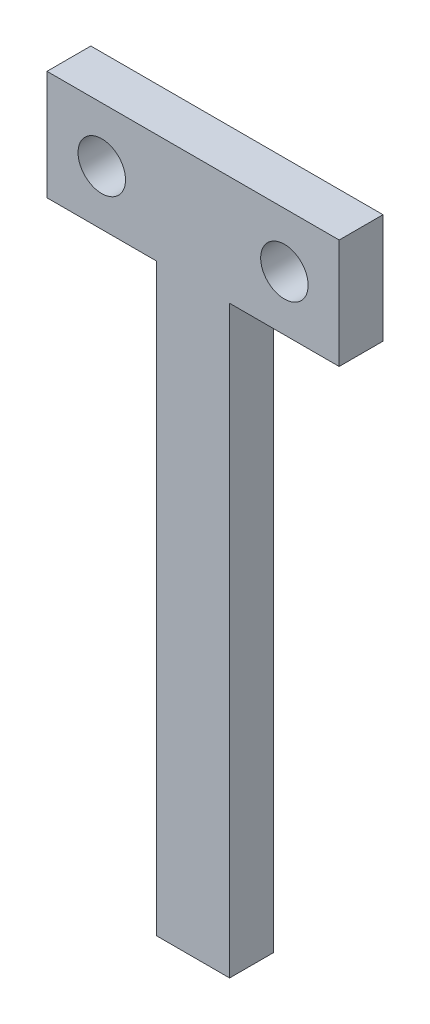
SolidWorks part; units mm, degrees
ref_plane "Front Plane" through (0, 0, 0) normal (0, 0, 1) x (1, 0, 0)
ref_plane "Top Plane" through (0, 0, 0) normal (0, 1, 0) x (1, 0, 0)
ref_plane "Right Plane" through (0, 0, 0) normal (1, 0, 0) x (0, 0, -1)
sketch "Sketch1" plane through (0, 0, 0) normal (0, 0, 1) x (1, 0, 0)
  line L0 (0, 0) -> (0, 40)
  line L1 (0, 40) -> (-7.5, 40)
  line L2 (-7.5, 40) -> (-7.5, 47.5)
  line L3 (-7.5, 47.5) -> (12.5, 47.5)
  line L4 (12.5, 47.5) -> (12.5, 40)
  line L5 (12.5, 40) -> (5, 40)
  line L6 (5, 40) -> (5, 0)
  line L7 (5, 0) -> (0, 0)
  circle A0 centre (-3.75, 43.75) radius 1.625
  circle A1 centre (8.75, 43.75) radius 1.625
  point P13 (12.5, 43.75)
  point P14 (0, 0)
  point P15 (-3.75, 40)
  point P16 (0, 0)
  point P17 (8.75, 40)
  dimension "D6" = 3.25
  dimension "D1" = 5
  dimension "D2" = 7.5
  dimension "D4" = 7.5
  dimension "D5" = 40
extrude "Boss-Extrude1" add sketch "Sketch1" along normal blind 3
